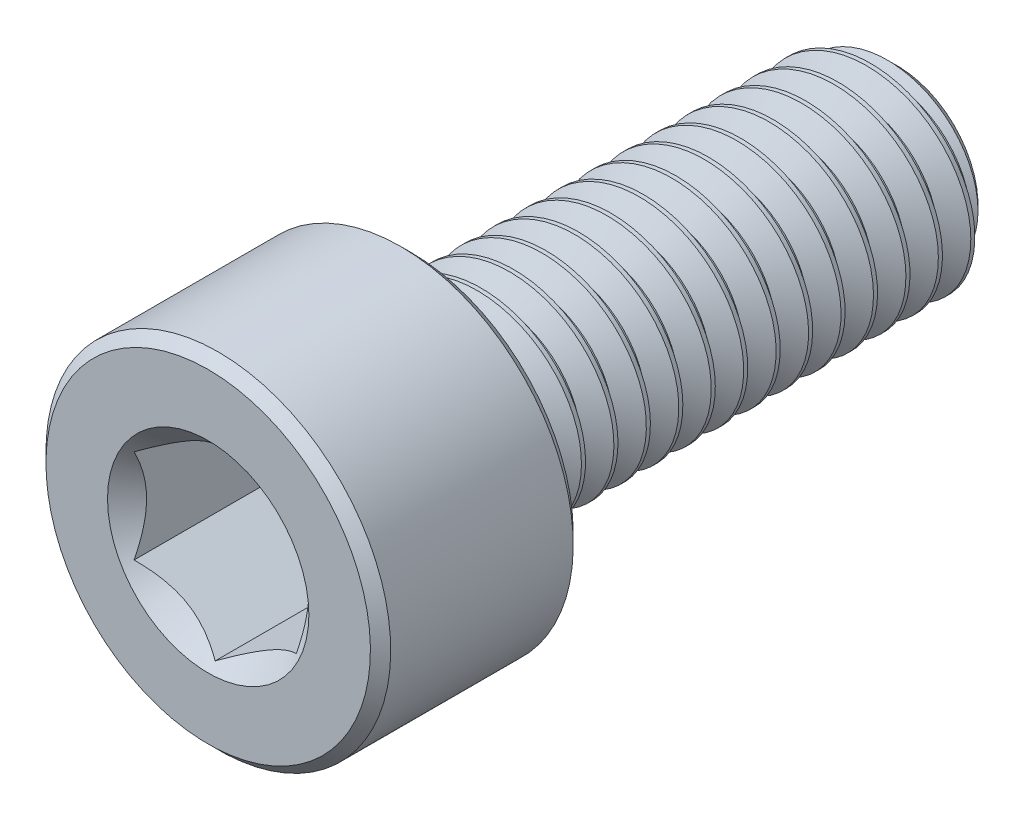
SolidWorks part; units mm, degrees
ref_plane "Front Plane" through (0, 0, 0) normal (0, 0, 1) x (1, 0, 0)
ref_plane "Top Plane" through (0, 0, 0) normal (0, 1, 0) x (1, 0, 0)
ref_plane "Right Plane" through (0, 0, 0) normal (1, 0, 0) x (0, 0, -1)
sketch "Sketch1" plane through (0, 0, 0) normal (1, 0, 0) x (0, 0, -1)
  line L0 (-8.5, 0) -> (8.5, 0) construction
  line L1 (8.5, 0) -> (8.5, 1.9804) construction
  line L2 (8.5, 1.9804) -> (7.9804, 2.5) construction
  line L3 (7.9804, 2.5) -> (7.9, 2.5) construction
  line L4 (7.9, 2.5) -> (-3.5, 2.5) construction
  line L5 (-3.5, 2.5) -> (-3.5, 4.25) construction
  line L6 (-3.5, 4.25) -> (-8.5, 4.25) construction
  line L7 (-8.5, 4.25) -> (-8.5, 0) construction
  line L8 (8.5, 1.9804) -> (8.5, 2.5) construction
  line L9 (8.45, 2.5866) -> (8.85, 1.8938) construction
  line L10 (8.85, 1.8938) -> (9.25, 2.5866) construction
  line L11 (9.25, 2.5866) -> (8.45, 2.5866) construction
  line L12 (8.85, 2.5866) -> (8.85, 2.5) construction
  line L13 (8.85, 1.8938) -> (8.85, 1.9804) construction
  line L14 (8.8, 1.9804) -> (8.9, 1.9804) construction
  line L15 (8.5, 2.5) -> (9.2, 2.5) construction
  line L16 (8.475, 2.5433) -> (9.225, 2.5433) construction
  line L17 (8.5, 0) -> (8.5, -2.5) construction
  line L18 (-3.75, 4.25) -> (-3.5, 4) construction
  line L19 (-8.25, 4.25) -> (-8.5, 4) construction
  line L20 (-3.5, 2.5) -> (-3.5, 0) construction
  line L21 (-3.5, 1.25) -> (0.5, 1.25) construction
  line L22 (0.5, 1.25) -> (4.5, 1.25) construction
  line L23 (4.5, 1.25) -> (8.5, 1.25) construction
  line L24 (0.5, 1.25) -> (0.5, 2.5) construction
  line L25 (0.5, 2.5) -> (0.5, 4.25) construction
  line L26 (4.5, 1.25) -> (4.5, 4.25) construction
  point P0 (-8.5, 2)
  point P3 (6.5, 2.5)
  point P4 (0, 0)
  point P18 (4.5, 2.5)
  point P22 (8.85, 1.9804)
  point P24 (7.9, 2.5)
  point P25 (8.85, 2.5)
  point P28 (8.85, 2.5433)
  point P29 (6.5, -2.5)
  point P30 (0.5, 2.5)
  point P31 (-6, 4.25)
  point P37 (-4.375, 4.25)
  point P38 (-8.125, 4.25)
  point P45 (0.5, 1.25)
  point P46 (4.5, 1.25)
  dimension "D2" = 0.1
  dimension "D7" = 0.25
  dimension "D8" = 0.25
  dimension "D9" = 0.25
  dimension "D10" = 0.125
  dimension "D11" = 0.625
  dimension "Drive Size" = 4
  dimension "Head Diameter" = 8.5
  dimension "Head Height" = 5
  dimension "Thread Pitch" = 0.8
  dimension "Thread Dia" = 5
  dimension "Length" = 12
  dimension "D12" = 0.6
  dimension "D4" = 2
  dimension "D3" = 45
sketch "Sketch2" plane through (0, 0, 0) normal (1, 0, 0) x (0, 0, -1)
  line L0 (-8.5, 0) -> (-8.5, 4)
  line L1 (-8.25, 4.25) -> (-3.75, 4.25)
  line L2 (-3.5, 4) -> (-3.5, 2.75)
  line L4 (7.9804, 2.5) -> (8.5, 1.9804)
  line L5 (8.5, 1.9804) -> (8.5, 0)
  line L6 (-3.5, 4.25) -> (-8.5, 4.25) construction
  line L7 (8.5, 0) -> (-8.5, 0)
  line L8 (-8.25, 4.25) -> (-8.5, 4) construction
  line L10 (-8.25, 4.25) -> (-8.5, 4)
  line L14 (-3.75, 4.25) -> (-3.5, 4) construction
  line L16 (-3.75, 4.25) -> (-3.5, 4)
  line L17 (-3.5, 2.5) -> (-3.5, 4.25) construction
  line L19 (-3.25, 2.5) -> (7.9804, 2.5)
  line L20 (7.9, 2.5) -> (-3.5, 2.5) construction
  arc A1 (-3.5, 2.75) -> (-3.25, 2.5) centre (-3.25, 2.75) ccw
  dimension "D3" = 0.25
revolve "Revolve1" add sketch "Sketch2" angle 360 about L7
sketch "Sketch3" plane through (0, 0, 8.5) normal (0, 0, 1) x (1, 0, 0)
  line L1 (2, -1.1547) -> (2, 1.1547)
  line L2 (2, 1.1547) -> (0, 2.3094)
  line L3 (0, 2.3094) -> (-2, 1.1547)
  line L4 (-2, 1.1547) -> (-2, -1.1547)
  line L5 (-2, -1.1547) -> (0, -2.3094)
  line L6 (0, -2.3094) -> (2, -1.1547)
  circle A0 centre (0, 0) radius 2 construction
  circle A1 centre (0, 0) radius 4.25 construction
  circle A2 centre (0, 0) radius 4.25 construction
  circle A3 centre (0, 0) radius 2.3094 construction
  point P13 (0, 0)
  dimension "D1" = 4.6188
extrude "Cut-Extrude1" cut sketch "Sketch3" against normal offset from surface (4 mm away) 1 up to face at (0, 4, 3.5)
sketch "Sketch4" plane through (0, 0, 8.5) normal (0, 0, 1) x (1, 0, 0)
  circle A0 centre (0, 0) radius 2.4826
  dimension "D1" = 4.9652
extrude "Cut-Extrude2" cut sketch "Sketch4" against normal up to vertex (2.5 mm away) draft 45 up to point (0, 4.25, 6)
sketch "Sketch11" plane through (0, 0, 0) normal (1, 0, 0) x (0, 0, -1)
  line L0 (-8.5, 0) -> (8.5, 0) construction
  line L1 (-8.5, 0) -> (8.5, 0) construction
  line L2 (-1.25, 0) -> (-1.25, 2.5) construction
  line L3 (7.9, 2.5) -> (-3.5, 2.5) construction
  line L4 (6.25, 0) -> (6.25, 2.5) construction
  line L6 (8.5, 1.9804) -> (8.5, 2.5) construction
  point P2 (-1.25, 0)
  point P3 (6.25, 0)
  dimension "D1" = 2.25
  dimension "D2" = 2.25
sketch "Sketch6" plane through (0, 0, -8.5) normal (0, 0, -1) x (-1, 0, 0)
  circle A0 centre (0, 0) radius 2.5
curve "Helix/Spiral1" pitch 0.8 height 12.8 turns 16
sketch "Sketch10" plane through (0, 0, 0) normal (1, 0, 0) x (0, 0, -1)
  line L0 (-3.25, -4.25) -> (-3.25, 4.25)
  line L5 (-8.5, 0) -> (8.5, 0) construction
  line L6 (-3.25, 2.5) -> (-3.25, -2.5) construction
  point P3 (-3.25, 0)
split "Split1" trim tools "Sketch10" bodies to split 106 resulting bodies 114 115
sketch "Sketch7" plane through (0, 0, 0) normal (1, 0, 0) x (0, 0, -1)
  line L0 (8.475, 2.5433) -> (9.225, 2.5433)
  line L1 (9.225, 2.5433) -> (8.9, 1.9804)
  line L2 (8.9, 1.9804) -> (8.8, 1.9804)
  line L3 (8.8, 1.9804) -> (8.475, 2.5433)
sweep "Cut-Sweep1" cut profiles "Sketch7" path "Helix/Spiral1" align with end faces yes
sketch "Sketch8" plane through (0, 0, 0) normal (1, 0, 0) x (0, 0, -1)
  line L0 (-3.5, 0) -> (-3.5, 2.5)
  line L1 (-3.25, -2.5) -> (-3.25, 2.5) construction
  line L2 (-3.5, 2.5) -> (-3.25, 2.5)
  line L4 (-3.25, 2.5) -> (-1.8066, 0)
  line L5 (-1.8066, 0) -> (-3.5, 0)
  line L6 (7.9, 2.5) -> (-3.5, 2.5) construction
  line L7 (-8.5, 0) -> (8.5, 0) construction
  dimension "D1" = 60
revolve "Revolve2" add sketch "Sketch8" angle 360 about L5
equation "\"D2@Sketch1\" = \"Thread Pitch@Sketch1\" / 8"
equation "\"D4@Helix/Spiral1\" = \"Thread Pitch@Sketch1\""
equation "\"D7@Sketch1\" = \"Head Height@Sketch1\" * .05"
equation "\"D8@Sketch1\"=\"D7@Sketch1\""
equation "\"D9@Sketch1\"=\"D7@Sketch1\""
equation "\"D10@Sketch1\"=\"D7@Sketch1\"/2"
equation "\"D11@Sketch1\"=\"D10@Sketch1\"*5"
equation "\"D4@Sketch1\"=\"Thread Pitch@Sketch1\"*2.5"
equation "\"D12@Sketch1\"=\"Thread Pitch@Sketch1\"*.75"
equation "\"D3@Helix/Spiral1\"=\"Length@Sketch1\"+\"Thread Pitch@Sketch1\""
equation "\"D3@Sketch2\"=\"Thread Dia@Sketch1\"*0.05"
equation "\"D1@Sketch11\"=\"Length@Sketch1\"*0.1875"
equation "\"D2@Sketch11\"=\"D1@Sketch11\""
equation "\"D1@Sketch4\"=\"D1@Sketch3\"*1.075"
